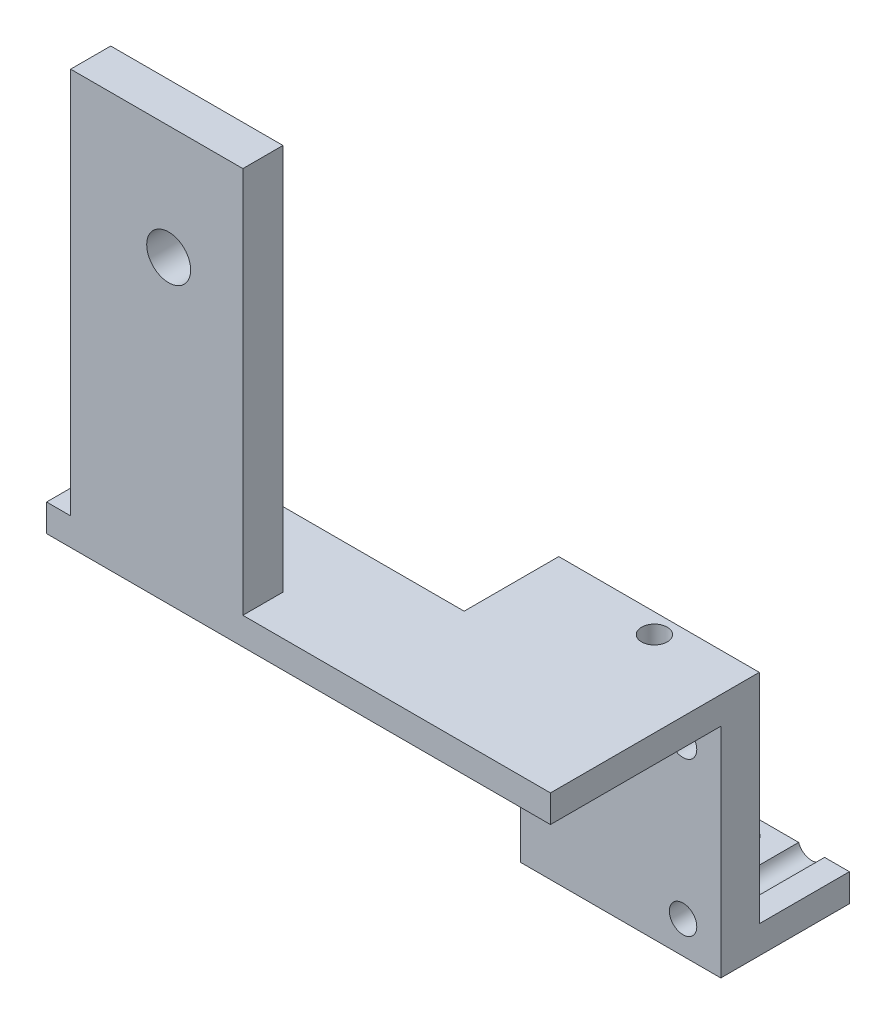
SolidWorks part; units mm, degrees
material "ABS"
ref_plane "Front Plane" through (0, 0, 0) normal (0, 0, 1) x (1, 0, 0)
ref_plane "Top Plane" through (0, 0, 0) normal (0, 1, 0) x (1, 0, 0)
ref_plane "Right Plane" through (0, 0, 0) normal (1, 0, 0) x (0, 0, -1)
sketch "Sketch1" plane through (0, 0, 0) normal (0, 0, 1) x (1, 0, 0)
  line L0 (14.173, 21.6872) -> (14.173, 3.958) construction
  line L1 (14.173, 12.8226) -> (-15.5119, 12.8226) construction
  line L2 (-6.655, 33.1426) -> (-6.655, 12.8226) construction
  line L3 (18.539, 25.421) -> (18.539, 28.59)
  line L4 (-4.633, 0.2242) -> (18.539, 0.2242)
  line L5 (-4.633, 0.2242) -> (-4.633, 25.421)
  line L6 (-4.633, 25.421) -> (18.539, 25.421)
  line L7 (18.539, 0.2242) -> (18.539, 25.421)
  line L8 (-4.633, 0.2242) -> (18.539, 25.421) construction
  line L9 (-4.633, 25.421) -> (18.539, 0.2242) construction
  line L10 (-16.1328, 39.7622) -> (3.2517, 39.7622)
  line L11 (-16.1328, 39.7622) -> (-16.1328, 0.2242)
  line L12 (-16.1328, 0.2242) -> (3.2517, 0.2242)
  line L13 (3.2517, 39.7622) -> (3.2517, 0.2242)
  line L14 (-16.1328, 39.7622) -> (3.2517, 0.2242) construction
  line L15 (-16.1328, 0.2242) -> (3.2517, 39.7622) construction
  line L16 (18.539, 28.59) -> (-4.633, 28.59)
  line L17 (-4.633, 28.59) -> (-4.633, 25.421)
  circle A0 centre (14.173, 21.6872) radius 1.5875
  circle A1 centre (14.173, 3.958) radius 1.5875
  circle A2 centre (-6.655, 33.1426) radius 2.54
  circle A3 centre (-6.655, 12.8226) radius 2.54
  point P10 (-6.4406, 19.9932)
  point P11 (6.953, 12.8226)
  dimension "D1" = 3.175
  dimension "D2" = 5.08
  dimension "D3" = 17.7292
  dimension "D4" = 20.32
  dimension "D5" = 20.828
  dimension "D6" = 21.463
extrude "Boss-Extrude1" add sketch "Sketch1" along normal blind 4.445 contours L6 L13 L4 L7 A1 A0 | L13 L6 L5 L4 | L3 L16 L13 L6 | L16 L17 L6 L13 region at (10.8954, 27.0055, 0) region at (10.7548, 12.8226, 0) region at (-0.6702, 12.8226, 0) region at (-0.6907, 27.0055, 0)
sketch "Sketch2" plane through (0, 0, 0) normal (0, 0, -1) x (-1, 0, 0)
  line L0 (-18.539, 3.4337) -> (-15.6715, 3.4337)
  line L1 (-18.539, 0.2242) -> (-18.539, 28.59) construction
  line L2 (-18.539, 3.4337) -> (-18.539, 0.2242)
  line L3 (-18.539, 0.2242) -> (4.633, 0.2242)
  line L4 (4.633, 0.2242) -> (4.633, 3.4337)
  line L5 (4.633, 0.2242) -> (4.633, 11.2852) construction
  line L6 (4.633, 3.4337) -> (-12.6746, 3.4337)
  circle A0 centre (-14.173, 3.958) radius 1.5875 construction
  arc A1 (-15.6715, 3.4337) -> (-12.6746, 3.4337) centre (-14.173, 3.958) ccw
extrude "Boss-Extrude2" add sketch "Sketch2" along normal blind 10.414
extrude "Boss-Extrude3" add sketch "Sketch1<6>" along normal blind 24.13 contours L3 L16 L13 L6 | L16 L17 L6 L13 region at (10.8954, 27.0055, 0) region at (-0.6907, 27.0055, 0)
sketch "Sketch1<6>" plane through (0, 0, 0) normal (0, 0, 1) x (1, 0, 0) same geometry as "Sketch1"
sketch "Sketch4" plane through (-4.633, 0, 0) normal (-1, 0, 0) x (0, 0, 1)
  line L0 (10.9334, 25.421) -> (10.9334, 28.59)
  line L1 (24.13, 28.59) -> (0, 28.59) construction
  line L2 (10.9334, 28.59) -> (24.13, 28.59)
  line L3 (24.13, 28.59) -> (24.13, 25.421)
  line L4 (24.13, 25.421) -> (10.9334, 25.421)
extrude "Boss-Extrude4" add sketch "Sketch4" along normal blind 35.052
sketch "Sketch5" plane through (0, 28.59, 0) normal (0, 1, 0) x (1, 0, 0)
  line L0 (-17.0054, -24.13) -> (-17.0054, -19.4975)
  line L1 (18.539, -24.13) -> (-39.685, -24.13) construction
  line L2 (-17.0054, -19.4975) -> (-36.9063, -19.4975)
  line L3 (-36.9063, -19.4975) -> (-36.9063, -24.13)
  line L4 (-36.9063, -24.13) -> (-17.0054, -24.13)
extrude "Boss-Extrude5" add sketch "Sketch5" along normal blind 44.704
sketch "Sketch6" plane through (0, 0, 19.4975) normal (0, 0, -1) x (-1, 0, 0)
  line L0 (17.0054, 73.294) -> (36.9063, 73.294) construction
  line L1 (17.0054, 73.294) -> (17.0054, 28.59) construction
  circle A0 centre (25.577, 60.1258) radius 2.54
  dimension "D1" = 5.08
  dimension "D2" = 13.1682
  dimension "D3" = 8.5716
extrude "Cut-Extrude1" cut sketch "Sketch6" against normal through all
sketch "Sketch7" plane through (0, 0.2242, 0) normal (0, -1, 0) x (1, 0, 0)
  circle A0 centre (-0.153, -2.7248) radius 1.9949
  circle A1 centre (8.6966, 2.2765) radius 1.4824
  circle A2 centre (8.6966, -7.7235) radius 1.561
extrude "Cut-Extrude2" cut sketch "Sketch7" against normal through all
